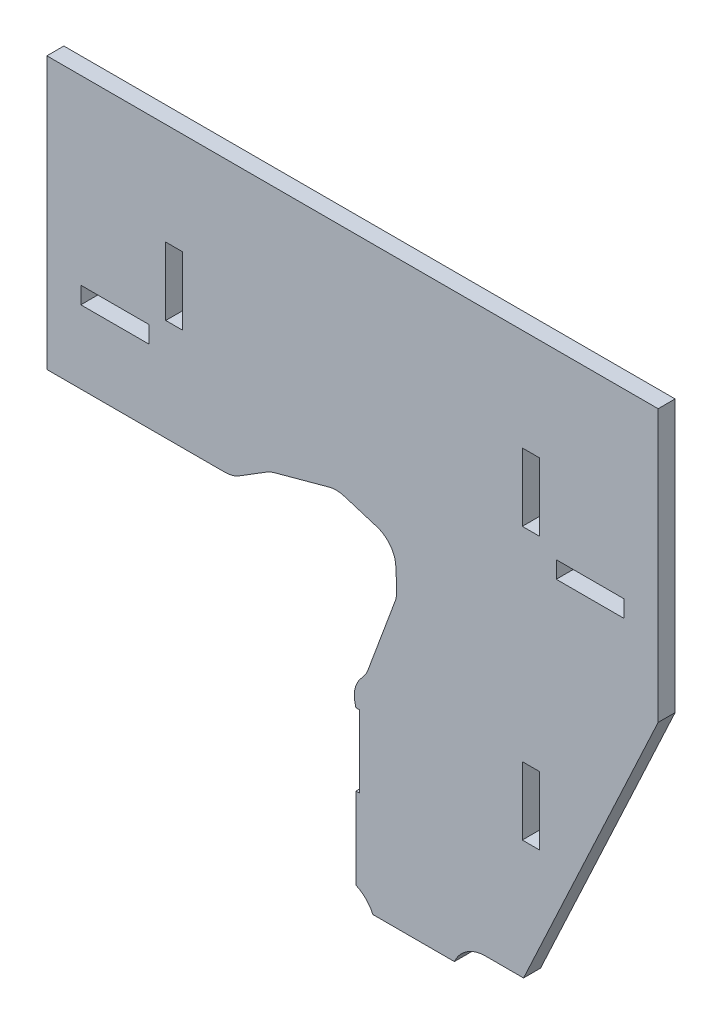
SolidWorks part; units mm, degrees
material "PBT General Purpose"
ref_plane "Front Plane" through (0, 0, 0) normal (0, 0, 1) x (1, 0, 0)
ref_plane "Top Plane" through (0, 0, 0) normal (0, 1, 0) x (1, 0, 0)
ref_plane "Right Plane" through (0, 0, 0) normal (1, 0, 0) x (0, 0, -1)
sketch "frame_outline" plane through (0, 0, 0) normal (0, 0, 1) x (1, 0, 0)
  line L0 (0, 0) -> (0, 0.3) construction
  line L1 (0, 0) -> (0.3, 0) construction
  line L2 (0, 0.3) -> (0.05, 0.3) construction
  line L3 (0.3, 0) -> (0.3, 0.05) construction
  line L4 (0.05, 0.3) -> (0.05, 1.5)
  line L5 (0.05, 1.5) -> (0.1, 1.5)
  line L6 (0.05, 0.3) -> (0.3, 0.3)
  line L7 (0.3, 0.3) -> (0.3, 0.05)
  line L8 (0.3, 0.05) -> (1.5, 0.05)
  line L9 (1.5, 0.05) -> (1.5, 0.35)
  line L10 (1.5, 0.35) -> (2.5182, 0.35)
  line L11 (2.5182, 0.35) -> (4.5, 4.6)
  line L12 (4.5, 4.6) -> (4.5, 8.6)
  line L13 (4.5, 8.6) -> (-4.5, 8.6)
  line L14 (-4.5, 8.6) -> (-4.5, 4.6)
  line L15 (-4.5, 4.6) -> (-1.7637, 4.6)
  line L16 (-1.7637, 4.6) -> (-1.2133, 4.9416)
  line L18 (0.1, 2.5625) -> (0.1, 1.5)
  line L19 (0, 8.6) -> (0, 0) construction
  line L20 (-2.5, 7.1) -> (2.5, 7.1) construction
  line L23 (-2.5, 7.1) -> (-2.75, 7.1)
  line L24 (-2.5, 7.1) -> (-2.5, 6.1)
  line L25 (-2.5, 6.1) -> (-2.75, 6.1)
  line L26 (-2.75, 7.1) -> (-2.75, 6.1)
  line L31 (2.5, 7.1) -> (2.75, 7.1)
  line L32 (2.5, 7.1) -> (2.5, 6.1)
  line L33 (2.5, 6.1) -> (2.75, 6.1)
  line L34 (2.75, 7.1) -> (2.75, 6.1)
  line L39 (2.5, 3.1) -> (2.75, 3.1)
  line L40 (2.5, 3.1) -> (2.5, 2.1)
  line L41 (2.5, 2.1) -> (2.75, 2.1)
  line L42 (2.75, 3.1) -> (2.75, 2.1)
  line L46 (-4, 5.925) -> (-3, 5.925)
  line L47 (-4, 5.925) -> (-4, 5.675)
  line L48 (-4, 5.675) -> (-3, 5.675)
  line L49 (-3, 5.925) -> (-3, 5.675)
  line L50 (3, 5.925) -> (4, 5.925)
  line L51 (3, 5.925) -> (3, 5.675)
  line L52 (3, 5.675) -> (4, 5.675)
  line L53 (4, 5.925) -> (4, 5.675)
  line L62 (-3, 5.8) -> (3, 5.8) construction
  line L63 (0.1, 2.5625) -> (0.05, 2.5625)
  line L64 (0.05, 2.5625) -> (-0.0089, 2.8119)
  line L65 (-0.0089, 2.8119) -> (0.2035, 3.0663)
  line L66 (0.2035, 3.0663) -> (0.655, 4.2832)
  line L67 (0.655, 4.2832) -> (0.6251, 4.9416)
  line L68 (0.6251, 4.9416) -> (-0.2329, 5.2084)
  line L69 (-0.2329, 5.2084) -> (-1.2133, 4.9416)
  point P40 (0, 7.1)
  point P64 (0, 3.0425)
  point P65 (0, 5.8)
  point P87 (2.625, 2.1)
  dimension "D2" = 0.3
  dimension "D3" = 0.05
  dimension "D4" = 0.05
  dimension "D5" = 1.2
  dimension "D6" = 1.2
  dimension "D7" = 0.05
  dimension "D8" = 0.3
  dimension "D10" = 9
  dimension "D13" = 4
  dimension "D14" = 8.6
  dimension "D15" = 4
  dimension "D16" = 5
  dimension "D17" = 0.25
  dimension "D18" = 0.25
  dimension "D20" = 1
  dimension "D21" = 1
  dimension "D22" = 1.5
  dimension "D29" = 3
  dimension "D9" = 155
  dimension "D11" = 0.1068
  dimension "D12" = 3
  dimension "D19" = 0.25
  dimension "D23" = 1
  dimension "D24" = 2.8
extrude "Boss-Extrude1" add sketch "frame_outline" along normal mid plane 0.25
fillet "Fillet1" radius 0.5 2 edges at (1.5, 0.35, 0) (0.3, 0.3, 0)
fillet "Fillet2" radius 0.4 7 edges at (-1.7637, 4.6, 0) (-1.2133, 4.9416, 0) (-0.2329, 5.2084, 0) (0.6251, 4.9416, 0) (0.655, 4.2832, 0) (0.2035, 3.0663, 0) (-0.0089, 2.8119, 0)
equation "\"t\"= 0.25'thickness of the sheets"
equation "\"t_cf\"= 0.115'thickness of single carbon fiber layer"
equation "\"t_kapton\"= 0.025'thickness of single Kapton flex layer"
equation "\"t_fr4\"= 0.1'thickness of FR4 with copper layer"
equation "\"joint_flex\"= 0.1'Width of flextures gap"
equation "\"joint_flex_eff\"= 0.02'Width of flecture after castelation"
equation "\"joint_fold\"= 0.2'Width of folding joints for 90deg fold"
equation "\"gap_tolerance\"= 0.002'Width to have interfecence fit between carbon fiber inserts"
equation "\"assemble_angle\"= 90'Angle of assembly parts"
equation "\"D3@frame_outline\" = \"joint_flex\" / 2"
equation "\"D4@frame_outline\" = \"joint_flex\" / 2"
equation "\"D17@frame_outline\"=\"t\""
equation "\"D18@frame_outline\"=\"t\""
equation "\"D1@Boss-Extrude1\"=\"t\""
equation "\"link_lift\"= 0.5'Actuation linkage amplification for the lift motion"
equation "\"link_swing\"= 0.45'Actuation linkage amplification for the swing motion"
equation "\"D19@frame_outline\"=\"t\""
